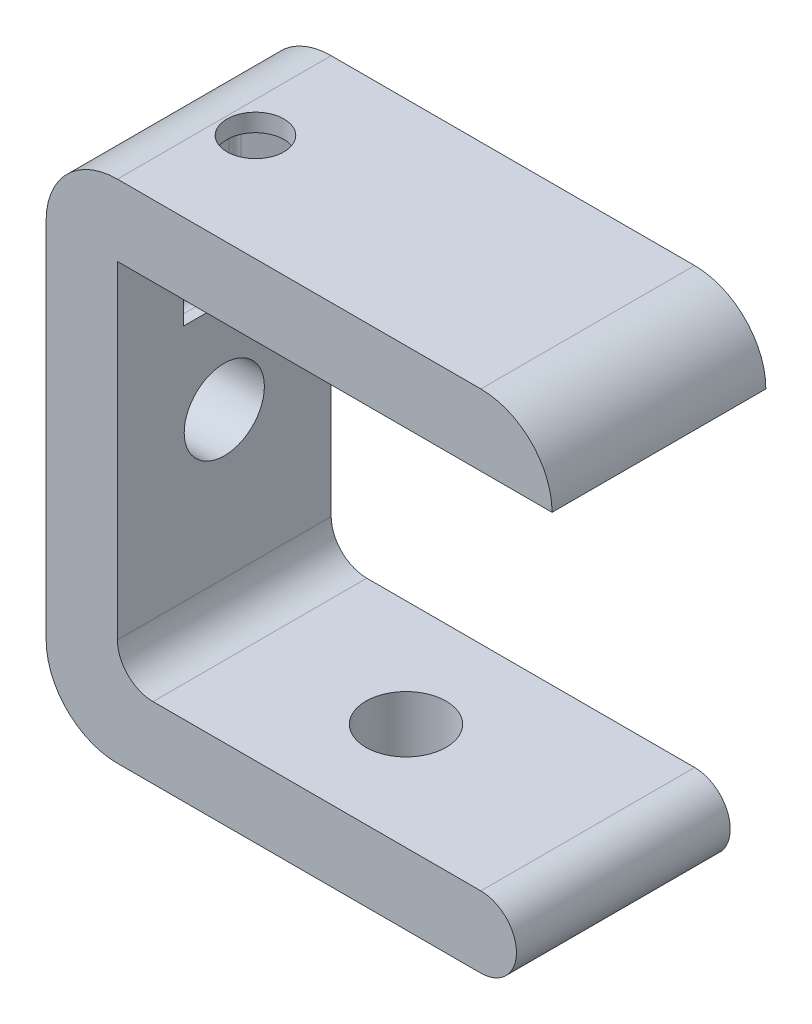
SolidWorks part; units mm, degrees
material "PET"
ref_plane "Plano frontal" through (0, 0, 0) normal (0, 0, 1) x (1, 0, 0)
ref_plane "Plano superior" through (0, 0, 0) normal (0, 1, 0) x (1, 0, 0)
ref_plane "Plano direito" through (0, 0, 0) normal (1, 0, 0) x (0, 0, -1)
sketch "Esboço1" plane through (0, 0, 0) normal (0, 0, 1) x (1, 0, 0)
  line L0 (-14.2, 14.2) -> (14.2, 14.2)
  line L1 (-10.2, 10.2) -> (10.2, 10.2)
  line L2 (-10.2, 10.2) -> (-10.2, -10.2)
  line L3 (-10.2, -10.2) -> (10.2, -10.2)
  line L4 (10.2, 10.2) -> (10.2, -10.2)
  line L5 (-10.2, 10.2) -> (10.2, -10.2) construction
  line L6 (-10.2, -10.2) -> (10.2, 10.2) construction
  line L7 (14.2, 14.2) -> (14.2, -14.2)
  line L8 (-14.2, -14.2) -> (14.2, -14.2)
  line L9 (-14.2, 14.2) -> (-14.2, -14.2)
  line L11 (10.2, 10.2) -> (14.2, 10.2)
  line L12 (10.2, 10.2) -> (10.2, -10.2)
  line L13 (10.2, -10.2) -> (14.2, -10.2)
  line L14 (14.2, 10.2) -> (14.2, -10.2)
  point P0 (0, 0)
  dimension "D1" = 20.4
  dimension "D2" = 20.4
  dimension "D3" = 4
extrude "Ressalto-extrusão1" add sketch "Esboço1" along normal mid plane 12 contours L13 L3 L2 L1 L11 L7 L0 L9 L8 region at (0, 13.7984, 0)
sketch "Esboço3" plane through (0, 14.2, 0) normal (0, 1, 0) x (1, 0, 0)
  line L0 (-14.2, 0) -> (14.2, 0) construction
  line L1 (-14.2, -6) -> (-14.2, 6) construction
  line L2 (14.2, -6) -> (14.2, 6) construction
  circle A0 centre (-8.45, 0) radius 1.6
  dimension "D1" = 5.75
  dimension "D2" = 3.2
extrude "Corte-extrusão1" cut sketch "Esboço3" against normal up to surface (4 mm away) up to face at (2, 10.2, 0)
sketch "Esboço4" plane through (0, 10.2, 0) normal (0, -1, 0) x (1, 0, 0)
  line L1 (-8.45, 3.2909) -> (-11.3, 1.6454)
  line L2 (-11.3, 1.6454) -> (-11.3, -1.6454)
  line L3 (-11.3, -1.6454) -> (-8.45, -3.2909)
  line L4 (-8.45, -3.2909) -> (-5.6, -1.6454)
  line L5 (-5.6, -1.6454) -> (-5.6, 1.6454)
  line L6 (-5.6, 1.6454) -> (-8.45, 3.2909)
  circle A0 centre (-8.45, 0) radius 2.85 construction
  dimension "D1" = 5.7
extrude "Corte-extrusão2" cut sketch "Esboço4" against normal blind 3
sketch "Esboço5" plane through (0, 10.2, 0) normal (0, -1, 0) x (1, 0, 0)
  line L4 (-10.2, -6) -> (14.2, -6)
  line L5 (-10.2, -6) -> (14.2, -6)
  line L6 (-8.45, 3.2909) -> (-11.3, 1.6454)
  line L7 (-11.3, 1.6454) -> (-11.3, -1.6454)
  line L8 (-11.3, -1.6454) -> (-8.45, -3.2909)
  line L9 (-8.45, -3.2909) -> (-5.6, -1.6454)
  line L10 (14.2, 6) -> (-10.2, 6)
  line L11 (14.2, 6) -> (-10.2, 6)
  line L12 (-8.45, -3.2909) -> (-10.2, -2.2805)
  line L13 (-8.45, -3.2909) -> (-10.2, -2.2805)
  line L14 (-10.2, -2.2805) -> (-10.2, -6)
  line L21 (-10.2, -2.2805) -> (-10.2, -6)
  line L22 (-10.2, 6) -> (-10.2, 2.2805)
  line L23 (-10.2, 6) -> (-10.2, 2.2805)
  line L24 (-10.2, 2.2805) -> (-8.45, 3.2909)
  line L25 (-10.2, 2.2805) -> (-8.45, 3.2909)
  line L26 (-8.45, 3.2909) -> (-5.6, 1.6454)
  line L27 (-8.45, 3.2909) -> (-5.6, 1.6454)
  line L28 (-5.6, 1.6454) -> (-5.6, -1.6454)
  line L29 (-5.6, 1.6454) -> (-5.6, -1.6454)
  line L30 (-5.6, -1.6454) -> (-5.6, 1.6454)
  line L31 (-5.6, 1.6454) -> (-8.45, 3.2909)
  line L32 (-8.45, 3.2909) -> (-11.3, 1.6454)
  line L33 (-11.3, 1.6454) -> (-11.3, -1.6454)
  line L34 (-11.3, -1.6454) -> (-8.45, -3.2909)
  line L35 (-8.45, -3.2909) -> (-5.6, -1.6454)
  line L36 (-5.6, -1.6454) -> (-5.6, 1.6454)
  line L37 (-5.6, 1.6454) -> (-8.45, 3.2909)
  line L38 (-5.6, -1.6454) -> (-8.45, -3.2909)
  line L39 (-5.6, -1.6454) -> (-8.45, -3.2909)
  line L40 (14.2, -6) -> (14.2, 6)
  line L41 (14.2, -6) -> (14.2, 6)
  line M17 (-8.45, -3.2909) -> (-10.2, -2.2805)
  line M23 (-10.2, 2.2805) -> (-8.45, 3.2909)
  line M24 (-8.45, 3.2909) -> (-5.6, 1.6454)
  line M25 (-5.6, 1.6454) -> (-5.6, -1.6454)
  line M26 (-5.6, -1.6454) -> (-8.45, -3.2909)
  dimension "D1" = 0
  dimension "D2" = 0
extrude "Corte-extrusão3" cut sketch "Esboço5" along normal blind 5 contours L33 L34 L32 M17 M26 M25 M24 M23 region at (-8.45, 10.2, 0)
fillet "Filete1" radius 0.5 3 edges at (-11.3, 9.2, 1.6454) (-11.3, 5.2, 0) (-11.3, 9.2, -1.6454)
fillet "Filete2" radius 4 4 edges at (-14.2, -14.2, 0) (-14.2, 14.2, 0) (14.2, 14.2, 0) (14.2, -14.2, 0)
fillet "Filete3" radius 2 2 edges at (-10.2, -10.2, 0) (14.2, -10.2, 0)
sketch "Esboço6" plane through (-14.2, 0, 0) normal (-1, 0, 0) x (0, 0, 1)
  circle A0 centre (0, 0) radius 2.25
  dimension "D1" = 4.5
extrude "Corte-extrusão4" cut sketch "Esboço6" against normal blind 10
sketch "Esboço7" plane through (0, -14.2, 0) normal (0, -1, 0) x (1, 0, 0)
  circle A0 centre (0, 0) radius 2.25
  dimension "D1" = 4.5
extrude "Corte-extrusão5" cut sketch "Esboço7" against normal blind 10
